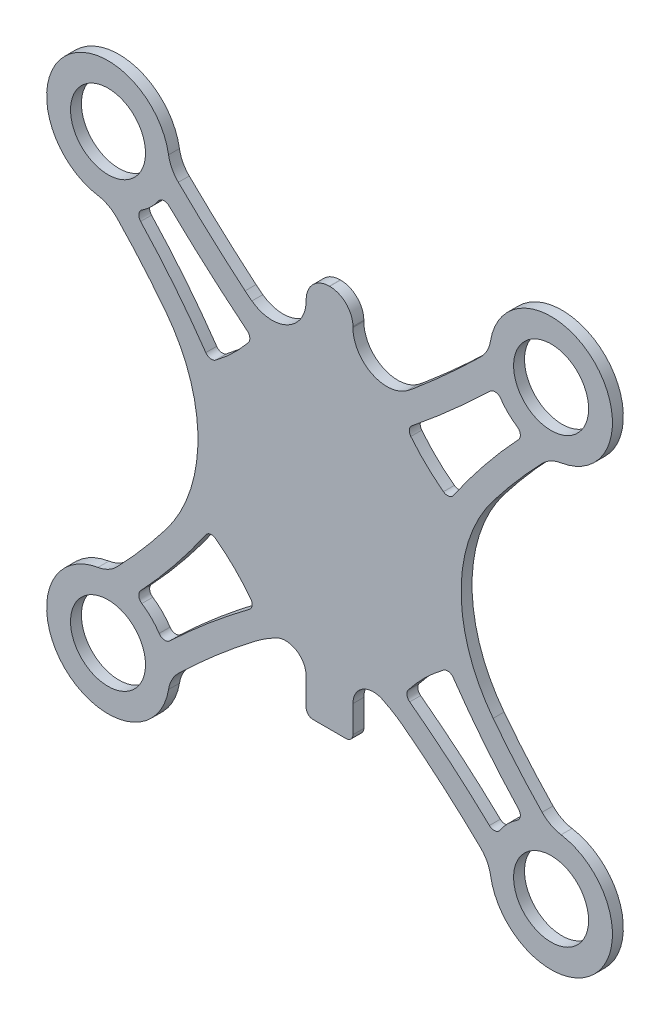
SolidWorks part; units mm, degrees
ref_plane "Front Plane" through (0, 0, 0) normal (0, 0, 1) x (1, 0, 0)
ref_plane "Top Plane" through (0, 0, 0) normal (0, 1, 0) x (1, 0, 0)
ref_plane "Right Plane" through (0, 0, 0) normal (1, 0, 0) x (0, 0, -1)
sketch "Sketch1" plane through (0, 0, 0) normal (0, 0, 1) x (1, 0, 0)
  line L0 (-32.5, 32.5) -> (32.5, -32.5) construction
  line L1 (-32.5, -32.5) -> (32.5, 32.5) construction
  line L2 (-32.5, -23.5) -> (-23.5, -32.5) construction
  line L3 (-19.304, 17.78) -> (19.304, 17.78) construction
  line L4 (-19.304, 17.78) -> (-19.304, -17.78) construction
  line L5 (-19.304, -17.78) -> (19.304, -17.78) construction
  line L6 (19.304, 17.78) -> (19.304, -17.78) construction
  line L7 (32.5, -23.5) -> (23.5, -32.5) construction
  line L8 (23.5, 32.5) -> (32.5, 23.5) construction
  line L9 (-32.5, 23.5) -> (-23.5, 32.5) construction
  line L10 (0, 17.78) -> (0, -17.78) construction
  line L11 (-19.304, 0) -> (19.304, 0) construction
  line L12 (-3.429, -22.1694) -> (-3.429, -26.178)
  line L13 (-2.429, -27.178) -> (2.429, -27.178)
  line L14 (3.429, -26.178) -> (3.429, -22.2297)
  line L15 (-3.429, 25.5442) -> (-3.429, 25.6764)
  line L16 (3.429, 25.6764) -> (3.429, 25.5442)
  line L17 (-0.0254, 29.08) -> (0.0254, 29.08)
  line L18 (-23.5, -32.5) -> (32.5, 23.5) construction
  line L19 (32.5, -23.5) -> (-23.5, 32.5) construction
  line L20 (-32.5, -23.5) -> (23.5, 32.5) construction
  line L21 (-32.5, 23.5) -> (23.5, -32.5) construction
  circle A0 centre (-32.5, -32.5) radius 30 construction
  circle A1 centre (32.5, -32.5) radius 30 construction
  circle A2 centre (32.5, 32.5) radius 30 construction
  circle A3 centre (-32.5, 32.5) radius 30 construction
  circle A4 centre (-32.5, -32.5) radius 5.5
  circle A5 centre (32.5, -32.5) radius 5.5
  circle A6 centre (32.5, 32.5) radius 5.5
  circle A7 centre (-32.5, 32.5) radius 5.5
  circle A8 centre (-32.5, -32.5) radius 9 construction
  circle A9 centre (32.5, -32.5) radius 9 construction
  circle A10 centre (32.5, 32.5) radius 9 construction
  circle A11 centre (-32.5, 32.5) radius 9 construction
  arc A12 (-12.3874, 22.3003) -> (-11.39, 21.5153) centre (0, 37.0135) ccw
  arc A13 (12.3874, 22.3003) -> (11.39, 21.5153) centre (0, 37.0135) cw
  arc A14 (2.429, -27.178) -> (3.429, -26.178) centre (2.429, -26.178) ccw
  arc A15 (-3.429, -26.178) -> (-2.429, -27.178) centre (-2.429, -26.178) ccw
  arc A16 (-10.9379, -21.4895) -> (10.9379, -21.4895) centre (0, -35.7605) cw construction
  arc A17 (-22.1695, -31.1889) -> (-10.9379, -21.4895) centre (66.4181, -122.4181) cw
  arc A18 (10.9379, -21.4895) -> (22.1695, -31.1889) centre (-66.4181, -122.4181) cw
  arc A19 (-12.3874, 22.3003) -> (12.3874, 22.3003) centre (0, 37.0135) ccw construction
  arc A20 (3.429, 25.6764) -> (0.0254, 29.08) centre (0.0254, 25.6764) ccw
  arc A21 (-3.429, 25.6764) -> (-0.0254, 29.08) centre (-0.0254, 25.6764) cw
  arc A22 (-22.1834, 31.1971) -> (-12.3874, 22.3003) centre (101.1226, 157.1226) ccw
  arc A23 (12.3874, 22.3003) -> (22.1834, 31.1971) centre (-101.1226, 157.1226) ccw
  arc A24 (-10.9379, -21.4895) -> (-7.8035, -19.5028) centre (1.7597, -38.0565) cw
  arc A25 (7.7165, -19.52) -> (10.9379, -21.4895) centre (0, -35.7605) cw
  arc A26 (3.429, 25.5442) -> (11.39, 21.5153) centre (8.429, 25.5442) ccw
  arc A27 (-3.429, 25.5442) -> (-11.39, 21.5153) centre (-8.429, 25.5442) cw
  arc A28 (7.7165, -19.52) -> (3.429, -22.2297) centre (6.429, -22.2297) ccw
  arc A29 (-7.8035, -19.5028) -> (-3.429, -22.1694) centre (-6.429, -22.1694) cw
  arc A30 (-31.1803, -22.155) -> (-23.9992, -13.8141) centre (-102.5742, 46.5742) ccw
  arc A31 (-23.9992, -13.8141) -> (-19.304, 0) centre (-41.9736, 0) ccw
  circle A32 centre (-32.5, -32.5) radius 26.4039 construction
  arc A33 (-19.304, 0) -> (-23.9992, 13.8141) centre (-41.9736, 0) ccw
  arc A34 (-23.4525, -27.7027) -> (-11.7612, -17.844) centre (66.4181, -122.4181) cw
  arc A35 (-16.7108, -11.3371) -> (-11.5639, -16.4112) centre (-32.5, -32.5) cw
  arc A36 (16.7108, -11.3371) -> (11.5639, -16.4112) centre (32.5, -32.5) ccw
  arc A37 (-31.1803, 22.155) -> (-23.9992, 13.8141) centre (-102.5742, -46.5742) cw
  arc A38 (23.4525, -27.7027) -> (11.7612, -17.844) centre (-66.4181, -122.4181) ccw
  arc A39 (-33.9673, -23.6204) -> (-23.6197, -33.9631) centre (-32.5, -32.5) ccw
  arc A40 (-27.5328, -24.9949) -> (-24.9987, -27.5271) centre (-32.5, -32.5) cw
  arc A41 (23.6197, -33.9631) -> (33.9673, -23.6204) centre (32.5, -32.5) ccw
  arc A42 (24.9987, -27.5271) -> (27.5328, -24.9949) centre (32.5, -32.5) cw
  circle A43 centre (-32.5, 32.5) radius 26.4039 construction
  arc A44 (-23.563, 27.5274) -> (-12.075, 17.381) centre (101.1226, 157.1226) ccw
  arc A45 (-16.7108, 11.3371) -> (-11.9227, 15.9548) centre (-32.5, 32.5) ccw
  arc A46 (23.563, 27.5274) -> (12.075, 17.381) centre (-101.1226, 157.1226) cw
  arc A47 (-27.714, -23.4536) -> (-18.155, -11.5751) centre (-102.5742, 46.5742) ccw
  arc A48 (16.7108, 11.3371) -> (11.9227, 15.9548) centre (32.5, 32.5) cw
  arc A49 (31.1803, 22.155) -> (23.9992, 13.8141) centre (102.5742, -46.5742) ccw
  arc A50 (-33.9673, 23.6204) -> (-23.6191, 33.9591) centre (-32.5, 32.5) cw
  arc A51 (-27.5328, 24.9949) -> (-25.1025, 27.3739) centre (-32.5, 32.5) ccw
  arc A52 (23.6191, 33.9591) -> (33.9673, 23.6204) centre (32.5, 32.5) cw
  arc A53 (25.1025, 27.3739) -> (27.5328, 24.9949) centre (32.5, 32.5) ccw
  arc A54 (19.304, 0) -> (23.9992, 13.8141) centre (41.9736, 0) cw
  arc A55 (27.714, -23.4536) -> (18.155, -11.5751) centre (102.5742, 46.5742) cw
  arc A56 (23.9992, -13.8141) -> (19.304, 0) centre (41.9736, 0) cw
  arc A57 (31.1803, -22.155) -> (23.9992, -13.8141) centre (102.5742, 46.5742) cw
  arc A58 (23.6197, -33.9631) -> (22.1695, -31.1889) centre (18.6862, -34.7759) ccw
  arc A59 (-27.714, 23.4536) -> (-18.155, 11.5751) centre (-102.5742, -46.5742) cw
  arc A60 (-23.6197, -33.9631) -> (-22.1695, -31.1889) centre (-18.6862, -34.7759) cw
  arc A61 (27.714, 23.4536) -> (18.155, 11.5751) centre (102.5742, -46.5742) ccw
  arc A62 (-18.155, -11.5751) -> (-16.7108, -11.3371) centre (-17.3183, -12.1514) cw
  arc A63 (-11.9227, 15.9548) -> (-12.075, 17.381) centre (-12.7145, 16.5915) ccw
  arc A64 (-25.1025, 27.3739) -> (-23.563, 27.5274) centre (-24.2674, 26.7952) cw
  arc A65 (-27.714, -23.4536) -> (-27.5328, -24.9949) centre (-26.972, -24.1477) ccw
  arc A66 (18.155, -11.5751) -> (16.7108, -11.3371) centre (17.3183, -12.1514) ccw
  arc A67 (23.563, 27.5274) -> (25.1025, 27.3739) centre (24.2674, 26.7952) cw
  arc A68 (11.5639, -16.4112) -> (11.7612, -17.844) centre (12.3695, -17.0303) ccw
  arc A69 (27.714, -23.4536) -> (27.5328, -24.9949) centre (26.972, -24.1477) cw
  arc A70 (27.714, 23.4536) -> (27.5328, 24.9949) centre (26.972, 24.1477) ccw
  arc A71 (23.4525, -27.7027) -> (24.9987, -27.5271) centre (24.1519, -26.9657) ccw
  arc A72 (18.155, 11.5751) -> (16.7108, 11.3371) centre (17.3183, 12.1514) cw
  arc A73 (-11.5639, -16.4112) -> (-11.7612, -17.844) centre (-12.3695, -17.0303) cw
  arc A74 (-18.155, 11.5751) -> (-16.7108, 11.3371) centre (-17.3183, 12.1514) ccw
  arc A75 (-23.4525, -27.7027) -> (-24.9987, -27.5271) centre (-24.1519, -26.9657) cw
  arc A76 (-27.714, 23.4536) -> (-27.5328, 24.9949) centre (-26.972, 24.1477) cw
  arc A77 (12.075, 17.381) -> (11.9227, 15.9548) centre (12.7145, 16.5915) ccw
  arc A78 (-31.1803, 22.155) -> (-33.9673, 23.6204) centre (-34.7824, 18.6873) ccw
  arc A79 (-23.6191, 33.9591) -> (-22.1834, 31.1971) centre (-18.6852, 34.7696) ccw
  arc A80 (33.9673, 23.6204) -> (31.1803, 22.155) centre (34.7824, 18.6873) ccw
  arc A81 (33.9673, -23.6204) -> (31.1803, -22.155) centre (34.7824, -18.6873) cw
  arc A82 (-33.9673, -23.6204) -> (-31.1803, -22.155) centre (-34.7824, -18.6873) ccw
  arc A83 (23.6191, 33.9591) -> (22.1834, 31.1971) centre (18.6852, 34.7696) cw
  point P5 (0, 0)
  point P19 (0, 17.78)
  point P20 (0, -17.78)
  point P21 (-19.304, 0)
  point P22 (19.304, 0)
  point P35 (-13.8296, -13.8296)
  point P45 (0, -27.178)
  point P46 (3.429, -18.11)
  point P50 (0, 29.08)
  point P53 (3.429, -27.178)
  point P56 (-3.429, -27.178)
  point P57 (0, 17.78)
  point P60 (0, -17.78)
  point P74 (3.429, 29.08)
  point P77 (-3.429, 29.08)
  point P105 (3.429, 18.0881)
  point P114 (-17.5727, -10.7205)
  point P117 (-28.6, -24.3889)
  point P131 (-3.429, 18.0881)
  point P134 (-18.1805, 10.3162)
  point P137 (-11.3018, 16.7582)
  point P140 (-24.48, 28.4159)
  point P141 (17.5727, -10.7205)
  point P143 (-28.6, 24.3889)
  point P146 (28.6, 24.3889)
  point P149 (24.48, 28.4159)
  point P152 (10.9504, -17.2428)
  point P153 (28.6, -24.3889)
  point P155 (18.1805, -10.3162)
  point P157 (28.6, 24.3889)
  point P158 (28.6, -24.3889)
  point P161 (24.3889, -28.6)
  point P164 (17.5727, 10.7205)
  point P167 (-10.9504, -17.2428)
  point P168 (-17.5727, 10.7205)
  point P170 (-28.6, -24.3889)
  point P172 (-24.3889, -28.6)
  point P174 (18.1805, 10.3162)
  point P177 (11.3018, 16.7582)
  point P179 (-28.6, 24.3889)
  dimension "D1" = 60
  dimension "D2" = 11
  dimension "D5" = 18
  dimension "D6" = 11.3
  dimension "D7" = 9.398
  dimension "D8" = 3
  dimension "D11" = 6.858
  dimension "D12" = 5
  dimension "D13" = 3.4036
  dimension "D14" = 1
  dimension "D15" = 1
  dimension "D16" = 3.4036
  dimension "D9" = 3
  dimension "D17" = 1.016
  dimension "D23" = 1.016
  dimension "D24" = 5
  dimension "D27" = 5
  dimension "D29" = 5
  dimension "D32" = 1.016
  dimension "D33" = 1.016
  dimension "D36" = 1.016
  dimension "D37" = 1.016
  dimension "D40" = 1.016
  dimension "D42" = 1.016
  dimension "D44" = 1.016
  dimension "D46" = 1.016
  dimension "D3" = 19.304
  dimension "D4" = 17.78
  dimension "D10" = 6.858
  dimension "D18" = 65
  dimension "D19" = 4
  dimension "D20" = 4
  dimension "D21" = 19.558
  dimension "D22" = 4.2
extrude "Boss-Extrude1" add sketch "Sketch1" along normal blind 1.6 contours A17 A24 A29 L12 A15 L13 A14 L14 A28 A25 A18 A58 A41 A81 A57 A56 A54 A49 A80 A52 A83 A23 A13 A26 L16 A20 L17 A21 L15 A27 A12 A22 A79 A50 A78 A37 A33 A31 A30 A82 A39 A60
extrude "Cut-Extrude3" cut sketch "Sketch1<5>" along normal through all contours A45 A63 A44 A64 A51 | A46 A77 A48 A69 A53 A67 | A6 | A5 | A38 A71 A42 A36 A68 | A75 A34 A73 A35 A72 A40 | A4 | A7 | A7 region at (-32.5, -32.5, 0) region at (32.5, -32.5, 0) region at (32.5, 32.5, 0) region at (-32.5, 32.5, 0) region at (-19.6446, -19.5292, 0) region at (19.6446, -19.5292, 0) region at (-19.799, 19.431, 0) region at (19.799, 19.431, 0)
sketch "Sketch1<5>" plane through (0, 0, 0) normal (0, 0, 1) x (1, 0, 0) same geometry as "Sketch1"
